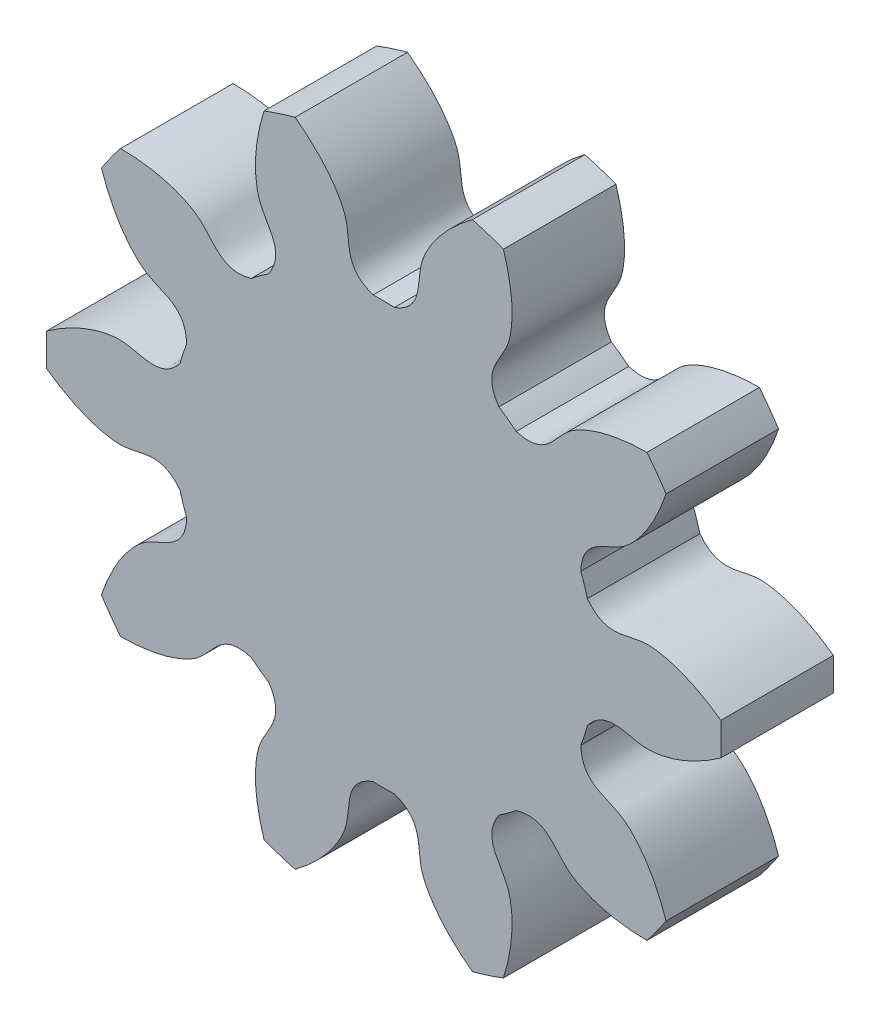
SolidWorks part; units mm, degrees
ref_plane "前视基准面" through (0, 0, 0) normal (0, 0, 1) x (1, 0, 0)
ref_plane "上视基准面" through (0, 0, 0) normal (0, 1, 0) x (1, 0, 0)
ref_plane "右视基准面" through (0, 0, 0) normal (1, 0, 0) x (0, 0, -1)
sketch "草图1" plane through (0, 0, 0) normal (0, 0, 1) x (1, 0, 0)
  circle A0 centre (0, 0) radius 12
extrude "凸台-拉伸1" add sketch "草图1" along normal blind 30
ref_axis "基准轴1" through (0, 0, -1.5) along (0, 0, 1)
sketch "草图2" plane through (0, 0, 0) normal (0, 0, 1) x (1, 0, 0)
  line L0 (0, 0) -> (0, 12) construction
  circle A0 centre (0, 0) radius 12 construction
  arc A1 (0.3809, 7.4903) -> (-0.3809, 7.4903) centre (0, 0) ccw
  arc A2 (8.5072, 13.3886) -> (-8.5072, 13.3886) centre (0, 0) ccw
  spline S0 degree 3 poles (0.3809, 7.4903) (1.4509, 7.8811) (1.1477, 8.7412) (1.3773, 9.4493) (1.389, 9.4831) (1.4027, 9.5201) (1.4184, 9.5604) (1.4364, 9.6038) (1.4568, 9.6502) (1.4797, 9.6997) (1.5052, 9.7521) (1.5335, 9.8073) (1.5646, 9.8653) (1.5987, 9.9258) (1.636, 9.989) (1.6765, 10.0545) (1.7203, 10.1225) (1.7675, 10.1926) (1.8184, 10.2648) (1.8728, 10.3391) (1.9311, 10.4152) (1.9932, 10.4931) (2.0592, 10.5726) (2.1293, 10.6537) (2.2035, 10.7361) (2.2819, 10.8197) (2.3646, 10.9045) (2.4516, 10.9902) (2.5431, 11.0768) (2.639, 11.164) (2.7395, 11.2518) (2.8447, 11.3399) (2.9545, 11.4283) (3.069, 11.5168) (3.1883, 11.6052) (3.3124, 11.6934) (3.4413, 11.7812) (3.5751, 11.8685) (3.7138, 11.9551) (3.8575, 12.0408) (4.0061, 12.1254) (4.1597, 12.2089) (4.3182, 12.291) (4.4818, 12.3716) (4.6503, 12.4505) (4.8238, 12.5275) (5.0022, 12.6025) (5.1856, 12.6753) (5.374, 12.7458) (5.5673, 12.8137) (5.7655, 12.8789) (5.9685, 12.9412) (6.1763, 13.0005) (6.389, 13.0566) (6.6063, 13.1093) (6.8284, 13.1585) (7.055, 13.2039) (7.2863, 13.2455) (7.522, 13.283) (7.7621, 13.3164) (8.0906, 13.3553) (8.3397, 13.3772) (8.5072, 13.3886) knots 0 0 0 0 0.201721 0.204697 0.208023 0.211699 0.215726 0.220102 0.224829 0.229906 0.235332 0.241109 0.247237 0.253714 0.260541 0.267719 0.275246 0.283124 0.291352 0.29993 0.308858 0.318136 0.327765 0.337743 0.348072 0.358751 0.36978 0.381158 0.392888 0.404967 0.417396 0.430176 0.443305 0.456785 0.470615 0.484795 0.499325 0.514205 0.529435 0.545016 0.560946 0.577227 0.593858 0.610839 0.62817 0.645851 0.663882 0.682264 0.700995 0.720077 0.739509 0.759291 0.779423 0.799905 0.820737 0.84192 0.863452 0.885335 0.907568 0.930151 0.953084 1 1 1 1
  spline S1 degree 3 poles (-0.3809, 7.4903) (-1.4509, 7.8811) (-1.1477, 8.7412) (-1.3773, 9.4493) (-1.389, 9.4831) (-1.4027, 9.5201) (-1.4184, 9.5604) (-1.4364, 9.6038) (-1.4568, 9.6502) (-1.4797, 9.6997) (-1.5052, 9.7521) (-1.5335, 9.8073) (-1.5646, 9.8653) (-1.5987, 9.9258) (-1.636, 9.989) (-1.6765, 10.0545) (-1.7203, 10.1225) (-1.7675, 10.1926) (-1.8184, 10.2648) (-1.8728, 10.3391) (-1.9311, 10.4152) (-1.9932, 10.4931) (-2.0592, 10.5726) (-2.1293, 10.6537) (-2.2035, 10.7361) (-2.2819, 10.8197) (-2.3646, 10.9045) (-2.4516, 10.9902) (-2.5431, 11.0768) (-2.639, 11.164) (-2.7395, 11.2518) (-2.8447, 11.3399) (-2.9545, 11.4283) (-3.069, 11.5168) (-3.1883, 11.6052) (-3.3124, 11.6934) (-3.4413, 11.7812) (-3.5751, 11.8685) (-3.7138, 11.9551) (-3.8575, 12.0408) (-4.0061, 12.1254) (-4.1597, 12.2089) (-4.3182, 12.291) (-4.4818, 12.3716) (-4.6503, 12.4505) (-4.8238, 12.5275) (-5.0022, 12.6025) (-5.1856, 12.6753) (-5.374, 12.7458) (-5.5673, 12.8137) (-5.7655, 12.8789) (-5.9685, 12.9412) (-6.1763, 13.0005) (-6.389, 13.0566) (-6.6063, 13.1093) (-6.8284, 13.1585) (-7.055, 13.2039) (-7.2863, 13.2455) (-7.522, 13.283) (-7.7621, 13.3164) (-8.0906, 13.3553) (-8.3397, 13.3772) (-8.5072, 13.3886) knots 0 0 0 0 0.201721 0.204697 0.208023 0.211699 0.215726 0.220102 0.224829 0.229906 0.235332 0.241109 0.247237 0.253714 0.260541 0.267719 0.275246 0.283124 0.291352 0.29993 0.308858 0.318136 0.327765 0.337743 0.348072 0.358751 0.36978 0.381158 0.392888 0.404967 0.417396 0.430176 0.443305 0.456785 0.470615 0.484795 0.499325 0.514205 0.529435 0.545016 0.560946 0.577227 0.593858 0.610839 0.62817 0.645851 0.663882 0.682264 0.700995 0.720077 0.739509 0.759291 0.779423 0.799905 0.820737 0.84192 0.863452 0.885335 0.907568 0.930151 0.953084 1 1 1 1
extrude "切除-拉伸1" cut sketch "草图2" along normal through all
pattern_circular "阵列(圆周)1" count 10 every 36 about axis through (0, 0, -1.5) along (0, 0, 1) of "切除-拉伸1"
sketch "草图3" plane through (0, 0, 0) normal (0, 0, 1) x (1, 0, 0)
  circle A0 centre (0, 0) radius 10 construction
  dimension "Dn" = 20
sketch "草图4" plane through (0, 0, 30) normal (0, 0, 1) x (1, 0, 0)
  arc A20 (-4.0945, 6.2837) -> (-4.7109, 5.8359) centre (0, 0) ccw
  arc A21 (-9.3561, 7.5142) -> (-10.0376, 6.5762) centre (0, 0) ccw
  arc A22 (-7.006, 2.6769) -> (-7.2414, 1.9524) centre (0, 0) ccw
  arc A23 (-11.986, 0.5797) -> (-11.986, -0.5797) centre (0, 0) ccw
  arc A24 (-7.2414, -1.9524) -> (-7.006, -2.6769) centre (0, 0) ccw
  arc A25 (-10.0376, -6.5762) -> (-9.3561, -7.5142) centre (0, 0) ccw
  arc A26 (-4.7109, -5.8359) -> (-4.0945, -6.2837) centre (0, 0) ccw
  arc A27 (-4.2552, -11.2202) -> (-3.1525, -11.5785) centre (0, 0) ccw
  arc A28 (-0.3809, -7.4903) -> (0.3809, -7.4903) centre (0, 0) ccw
  arc A29 (3.1525, -11.5785) -> (4.2552, -11.2202) centre (0, 0) ccw
  arc A30 (4.0945, -6.2837) -> (4.7109, -5.8359) centre (0, 0) ccw
  arc A31 (9.3561, -7.5142) -> (10.0376, -6.5762) centre (0, 0) ccw
  arc A32 (7.006, -2.6769) -> (7.2414, -1.9524) centre (0, 0) ccw
  arc A33 (11.986, -0.5797) -> (11.986, 0.5797) centre (0, 0) ccw
  arc A34 (7.2414, 1.9524) -> (7.006, 2.6769) centre (0, 0) ccw
  arc A35 (10.0376, 6.5762) -> (9.3561, 7.5142) centre (0, 0) ccw
  arc A36 (4.7109, 5.8359) -> (4.0945, 6.2837) centre (0, 0) ccw
  arc A37 (4.2552, 11.2202) -> (3.1525, 11.5785) centre (0, 0) ccw
  arc A38 (0.3809, 7.4903) -> (-0.3809, 7.4903) centre (0, 0) ccw
  arc A39 (-3.1525, 11.5785) -> (-4.2552, 11.2202) centre (0, 0) ccw
  arc A40 (-4.0945, 6.2837) -> (-4.7109, 5.8359) centre (0, 0) ccw
  arc A41 (-9.3561, 7.5142) -> (-10.0376, 6.5762) centre (0, 0) ccw
  arc A42 (-7.006, 2.6769) -> (-7.2414, 1.9524) centre (0, 0) ccw
  arc A43 (-11.986, 0.5797) -> (-11.986, -0.5797) centre (0, 0) ccw
  arc A44 (-7.2414, -1.9524) -> (-7.006, -2.6769) centre (0, 0) ccw
  arc A45 (-10.0376, -6.5762) -> (-9.3561, -7.5142) centre (0, 0) ccw
  arc A46 (-4.7109, -5.8359) -> (-4.0945, -6.2837) centre (0, 0) ccw
  arc A47 (-4.2552, -11.2202) -> (-3.1525, -11.5785) centre (0, 0) ccw
  arc A48 (-0.3809, -7.4903) -> (0.3809, -7.4903) centre (0, 0) ccw
  arc A49 (3.1525, -11.5785) -> (4.2552, -11.2202) centre (0, 0) ccw
  arc A50 (4.0945, -6.2837) -> (4.7109, -5.8359) centre (0, 0) ccw
  arc A51 (9.3561, -7.5142) -> (10.0376, -6.5762) centre (0, 0) ccw
  arc A52 (7.006, -2.6769) -> (7.2414, -1.9524) centre (0, 0) ccw
  arc A53 (11.986, -0.5797) -> (11.986, 0.5797) centre (0, 0) ccw
  arc A54 (7.2414, 1.9524) -> (7.006, 2.6769) centre (0, 0) ccw
  arc A55 (10.0376, 6.5762) -> (9.3561, 7.5142) centre (0, 0) ccw
  arc A56 (4.7109, 5.8359) -> (4.0945, 6.2837) centre (0, 0) ccw
  arc A57 (4.2552, 11.2202) -> (3.1525, 11.5785) centre (0, 0) ccw
  arc A58 (0.3809, 7.4903) -> (-0.3809, 7.4903) centre (0, 0) ccw
  arc A59 (-3.1525, 11.5785) -> (-4.2552, 11.2202) centre (0, 0) ccw
  spline S20 degree 3 poles (2357.9896, 3233.0149) (-45.5111, -76.1208) (0.8912, 1.3359) (-6.6791, 6.8428) (-6.7335, 6.8799) (-6.81, 6.9276) (-6.9015, 6.9798) (-7.0083, 7.0352) (-7.1308, 7.0926) (-7.2694, 7.151) (-7.4243, 7.2091) (-7.5956, 7.2657) (-7.7836, 7.3195) (-7.9881, 7.3693) (-8.2093, 7.4139) (-8.4468, 7.452) (-8.7007, 7.4824) (-8.9705, 7.5038) (-41.9663, 8.7956) (-79.134, -211.6177) (2738.2164, 2912.7683) knots -1.870678 -1.870678 -1.870678 -1.870678 0.735149 0.738125 0.745127 0.75353 0.763333 0.774537 0.787142 0.801147 0.816552 0.833358 0.851564 0.871171 0.892178 0.914586 0.938395 0.963603 0.990213 10.164096 10.164096 10.164096 10.164096 only from (-4.7109, 5.8359) to (-9.3561, 7.5142)
  spline S21 degree 3 poles (-1900.4629, -3517.2649) (168.6597, 144.2035) (-22.0225, 35.4119) (-9.8048, 5.9626) (-9.6975, 5.7306) (-9.5878, 5.5164) (-9.4771, 5.3199) (-9.3665, 5.1408) (-9.2572, 4.9787) (-9.1505, 4.8332) (-9.0474, 4.7038) (-8.9491, 4.5901) (-8.8565, 4.4913) (-8.7709, 4.4068) (-8.693, 4.336) (-8.6239, 4.2779) (-8.5719, 4.2376) (-0.9951, -1.2604) (58.3315, 66.8063) (-2346.1255, -3241.6441) knots -8.822355 -8.822355 -8.822355 -8.822355 0.036397 0.061605 0.085414 0.107822 0.128829 0.148436 0.166642 0.183448 0.198853 0.212858 0.225463 0.236667 0.24647 0.254873 0.261875 0.264851 2.87068 2.87068 2.87068 2.87068 only from (-10.0376, 6.5762) to (-7.006, 2.6769)
  spline S22 degree 3 poles (7.3352, 4001.5555) (7.9234, -88.3337) (-0.0642, 1.6046) (-9.4256, 1.6101) (-9.4914, 1.6081) (-9.5814, 1.6018) (-9.686, 1.5902) (-9.805, 1.5722) (-9.9379, 1.5467) (-10.0843, 1.5125) (-10.2438, 1.4684) (-10.4157, 1.4134) (-10.5993, 1.3465) (-10.7941, 1.2666) (-10.9992, 1.1727) (-11.2138, 1.0639) (-11.437, 0.9392) (-11.6679, 0.7979) (-39.1213, -17.5514) (60.365, -217.7161) (503.1813, 3965.9623) knots -1.870678 -1.870678 -1.870678 -1.870678 0.735149 0.738125 0.745127 0.75353 0.763333 0.774537 0.787142 0.801147 0.816552 0.833358 0.851564 0.871171 0.892178 0.914586 0.938395 0.963603 0.990213 10.164096 10.164096 10.164096 10.164096 only from (-7.2414, 1.9524) to (-11.986, 0.5797)
  spline S23 degree 3 poles (529.8897, -3962.5911) (51.6878, 215.7988) (-38.6312, 15.7043) (-11.437, -0.9392) (-11.2138, -1.0639) (-10.9992, -1.1727) (-10.7941, -1.2666) (-10.5993, -1.3465) (-10.4157, -1.4134) (-10.2438, -1.4684) (-10.0843, -1.5125) (-9.9379, -1.5467) (-9.805, -1.5722) (-9.686, -1.5902) (-9.5814, -1.6018) (-9.4914, -1.6081) (-9.4256, -1.6101) (-0.0642, -1.6046) (7.9234, 88.3338) (7.3352, -4001.5632) knots -8.822355 -8.822355 -8.822355 -8.822355 0.036397 0.061605 0.085414 0.107822 0.128829 0.148436 0.166642 0.183448 0.198853 0.212858 0.225463 0.236667 0.24647 0.254873 0.261875 0.264851 2.87068 2.87068 2.87068 2.87068 only from (-11.986, -0.5797) to (-7.2414, -1.9524)
  spline S24 degree 3 poles (-2346.121, 3241.6379) (58.3315, -66.8062) (-0.9952, 1.2604) (-8.5719, -4.2376) (-8.6239, -4.2779) (-8.693, -4.336) (-8.7709, -4.4068) (-8.8565, -4.4913) (-8.9491, -4.5901) (-9.0474, -4.7038) (-9.1505, -4.8332) (-9.2572, -4.9787) (-9.3665, -5.1408) (-9.4771, -5.3199) (-9.5878, -5.5164) (-9.6975, -5.7306) (-9.8048, -5.9626) (-9.9085, -6.2127) (-21.3334, -37.1943) (176.8067, -140.6544) (-1924.0519, 3504.2934) knots -1.870678 -1.870678 -1.870678 -1.870678 0.735149 0.738125 0.745127 0.75353 0.763333 0.774537 0.787142 0.801147 0.816552 0.833358 0.851564 0.871171 0.892178 0.914586 0.938395 0.963603 0.990213 10.164096 10.164096 10.164096 10.164096 only from (-7.006, -2.6769) to (-10.0376, -6.5762)
  spline S25 degree 3 poles (2757.8424, -2894.3422) (-85.027, 204.9662) (-40.4841, -10.0018) (-8.7007, -7.4824) (-8.4468, -7.452) (-8.2093, -7.4139) (-7.9881, -7.3693) (-7.7836, -7.3195) (-7.5956, -7.2657) (-7.4243, -7.2091) (-7.2694, -7.151) (-7.1308, -7.0926) (-7.0083, -7.0352) (-6.9015, -6.9798) (-6.81, -6.9277) (-6.7335, -6.8799) (-6.6791, -6.8428) (0.8912, -1.3359) (-45.5111, 76.1209) (2357.9941, -3233.0211) knots -8.822355 -8.822355 -8.822355 -8.822355 0.036397 0.061605 0.085414 0.107822 0.128829 0.148436 0.166642 0.183448 0.198853 0.212858 0.225463 0.236667 0.24647 0.254873 0.261875 0.264851 2.87068 2.87068 2.87068 2.87068 only from (-9.3561, -7.5142) to (-4.7109, -5.8359)
  spline S26 degree 3 poles (-3803.4388, 1243.5248) (86.4588, -19.761) (-1.546, 0.4348) (-4.444, -8.4668) (-4.4624, -8.5299) (-4.4842, -8.6175) (-4.5055, -8.7206) (-4.5252, -8.8393) (-4.542, -8.9735) (-4.5547, -9.1234) (-4.562, -9.2886) (-4.5629, -9.4691) (-4.556, -9.6645) (-4.5402, -9.8744) (-4.5142, -10.0985) (-4.4771, -10.3362) (-4.4275, -10.587) (-4.3645, -10.8503) (4.6032, -42.6303) (225.7141, -9.8674) (-3616.3627, 1704.1036) knots -1.870678 -1.870678 -1.870678 -1.870678 0.735149 0.738125 0.745127 0.75353 0.763333 0.774537 0.787142 0.801147 0.816552 0.833358 0.851564 0.871171 0.892178 0.914586 0.938395 0.963603 0.990213 10.164096 10.164096 10.164096 10.164096 only from (-4.0945, -6.2837) to (-4.2552, -11.2202)
  spline S27 degree 3 poles (3932.393, -720.553) (-189.2644, 115.8435) (-26.8734, -31.8875) (-2.641, -11.1675) (-2.4534, -10.9937) (-2.2836, -10.8233) (-2.131, -10.6572) (-1.9948, -10.4967) (-1.8744, -10.3427) (-1.769, -10.1962) (-1.6778, -10.0581) (-1.6, -9.9295) (-1.5346, -9.8109) (-1.4808, -9.7034) (-1.4375, -9.6074) (-1.4036, -9.5238) (-1.3814, -9.4619) (1.5063, -0.5569) (-81.562, 34.8323) (3807.9794, -1229.5749) knots -8.822355 -8.822355 -8.822355 -8.822355 0.036397 0.061605 0.085414 0.107822 0.128829 0.148436 0.166642 0.183448 0.198853 0.212858 0.225463 0.236667 0.24647 0.254873 0.261875 0.264851 2.87068 2.87068 2.87068 2.87068 only from (-3.1525, -11.5785) to (-0.3809, -7.4903)
  spline S28 degree 3 poles (-3807.9721, -1229.5725) (81.5619, 34.8323) (-1.5063, -0.557) (1.3814, -9.4619) (1.4036, -9.5238) (1.4375, -9.6074) (1.4808, -9.7034) (1.5346, -9.8109) (1.6, -9.9295) (1.6778, -10.0581) (1.769, -10.1962) (1.8744, -10.3427) (1.9948, -10.4967) (2.131, -10.6572) (2.2836, -10.8233) (2.4534, -10.9937) (2.641, -11.1675) (2.8467, -11.3434) (28.7815, -31.7829) (188.4065, 124.6885) (-3927.3458, -746.9958) knots -1.870678 -1.870678 -1.870678 -1.870678 0.735149 0.738125 0.745127 0.75353 0.763333 0.774537 0.787142 0.801147 0.816552 0.833358 0.851564 0.871171 0.892178 0.914586 0.938395 0.963603 0.990213 10.164096 10.164096 10.164096 10.164096 only from (0.3809, -7.4903) to (3.1525, -11.5785)
  spline S29 degree 3 poles (3604.9032, 1728.463) (-221.2093, -17.5274) (-2.998, -41.5933) (4.4275, -10.587) (4.4771, -10.3362) (4.5142, -10.0985) (4.5402, -9.8744) (4.556, -9.6645) (4.5629, -9.4691) (4.562, -9.2886) (4.5547, -9.1234) (4.542, -8.9735) (4.5252, -8.8393) (4.5055, -8.7206) (4.4842, -8.6175) (4.4624, -8.5299) (4.444, -8.4668) (1.5459, 0.4348) (-86.459, -19.761) (3803.446, 1243.5272) knots -8.822355 -8.822355 -8.822355 -8.822355 0.036397 0.061605 0.085414 0.107822 0.128829 0.148436 0.166642 0.183448 0.198853 0.212858 0.225463 0.236667 0.24647 0.254873 0.261875 0.264851 2.87068 2.87068 2.87068 2.87068 only from (4.2552, -11.2202) to (4.0945, -6.2837)
  spline S30 degree 3 poles (-2357.9896, -3233.0149) (45.5111, 76.1208) (-0.8912, -1.3359) (6.6791, -6.8428) (6.7335, -6.8799) (6.81, -6.9276) (6.9015, -6.9798) (7.0083, -7.0352) (7.1308, -7.0926) (7.2694, -7.151) (7.4243, -7.2091) (7.5956, -7.2657) (7.7836, -7.3195) (7.9881, -7.3693) (8.2093, -7.4139) (8.4468, -7.452) (8.7007, -7.4824) (8.9705, -7.5038) (41.9663, -8.7956) (79.134, 211.6177) (-2738.2164, -2912.7683) knots -1.870678 -1.870678 -1.870678 -1.870678 0.735149 0.738125 0.745127 0.75353 0.763333 0.774537 0.787142 0.801147 0.816552 0.833358 0.851564 0.871171 0.892178 0.914586 0.938395 0.963603 0.990213 10.164096 10.164096 10.164096 10.164096 only from (4.7109, -5.8359) to (9.3561, -7.5142)
  spline S31 degree 3 poles (1900.4629, 3517.2649) (-168.6597, -144.2035) (22.0225, -35.4119) (9.8048, -5.9626) (9.6975, -5.7306) (9.5878, -5.5164) (9.4771, -5.3199) (9.3665, -5.1408) (9.2572, -4.9787) (9.1505, -4.8332) (9.0474, -4.7038) (8.9491, -4.5901) (8.8565, -4.4913) (8.7709, -4.4068) (8.693, -4.336) (8.6239, -4.2779) (8.5719, -4.2376) (0.9951, 1.2604) (-58.3315, -66.8063) (2346.1255, 3241.6441) knots -8.822355 -8.822355 -8.822355 -8.822355 0.036397 0.061605 0.085414 0.107822 0.128829 0.148436 0.166642 0.183448 0.198853 0.212858 0.225463 0.236667 0.24647 0.254873 0.261875 0.264851 2.87068 2.87068 2.87068 2.87068 only from (10.0376, -6.5762) to (7.006, -2.6769)
  spline S32 degree 3 poles (-7.3352, -4001.5555) (-7.9234, 88.3337) (0.0642, -1.6046) (9.4256, -1.6101) (9.4914, -1.6081) (9.5814, -1.6018) (9.686, -1.5902) (9.805, -1.5722) (9.9379, -1.5467) (10.0843, -1.5125) (10.2438, -1.4684) (10.4157, -1.4134) (10.5993, -1.3465) (10.7941, -1.2666) (10.9992, -1.1727) (11.2138, -1.0639) (11.437, -0.9392) (11.6679, -0.7979) (39.1213, 17.5514) (-60.365, 217.7161) (-503.1813, -3965.9623) knots -1.870678 -1.870678 -1.870678 -1.870678 0.735149 0.738125 0.745127 0.75353 0.763333 0.774537 0.787142 0.801147 0.816552 0.833358 0.851564 0.871171 0.892178 0.914586 0.938395 0.963603 0.990213 10.164096 10.164096 10.164096 10.164096 only from (7.2414, -1.9524) to (11.986, -0.5797)
  spline S33 degree 3 poles (-529.8897, 3962.5911) (-51.6878, -215.7988) (38.6312, -15.7043) (11.437, 0.9392) (11.2138, 1.0639) (10.9992, 1.1727) (10.7941, 1.2666) (10.5993, 1.3465) (10.4157, 1.4134) (10.2438, 1.4684) (10.0843, 1.5125) (9.9379, 1.5467) (9.805, 1.5722) (9.686, 1.5902) (9.5814, 1.6018) (9.4914, 1.6081) (9.4256, 1.6101) (0.0642, 1.6046) (-7.9234, -88.3338) (-7.3352, 4001.5632) knots -8.822355 -8.822355 -8.822355 -8.822355 0.036397 0.061605 0.085414 0.107822 0.128829 0.148436 0.166642 0.183448 0.198853 0.212858 0.225463 0.236667 0.24647 0.254873 0.261875 0.264851 2.87068 2.87068 2.87068 2.87068 only from (11.986, 0.5797) to (7.2414, 1.9524)
  spline S34 degree 3 poles (2346.121, -3241.6379) (-58.3315, 66.8062) (0.9952, -1.2604) (8.5719, 4.2376) (8.6239, 4.2779) (8.693, 4.336) (8.7709, 4.4068) (8.8565, 4.4913) (8.9491, 4.5901) (9.0474, 4.7038) (9.1505, 4.8332) (9.2572, 4.9787) (9.3665, 5.1408) (9.4771, 5.3199) (9.5878, 5.5164) (9.6975, 5.7306) (9.8048, 5.9626) (9.9085, 6.2127) (21.3334, 37.1943) (-176.8067, 140.6544) (1924.0519, -3504.2934) knots -1.870678 -1.870678 -1.870678 -1.870678 0.735149 0.738125 0.745127 0.75353 0.763333 0.774537 0.787142 0.801147 0.816552 0.833358 0.851564 0.871171 0.892178 0.914586 0.938395 0.963603 0.990213 10.164096 10.164096 10.164096 10.164096 only from (7.006, 2.6769) to (10.0376, 6.5762)
  spline S35 degree 3 poles (-2757.8424, 2894.3422) (85.027, -204.9662) (40.4841, 10.0018) (8.7007, 7.4824) (8.4468, 7.452) (8.2093, 7.4139) (7.9881, 7.3693) (7.7836, 7.3195) (7.5956, 7.2657) (7.4243, 7.2091) (7.2694, 7.151) (7.1308, 7.0926) (7.0083, 7.0352) (6.9015, 6.9798) (6.81, 6.9277) (6.7335, 6.8799) (6.6791, 6.8428) (-0.8912, 1.3359) (45.5111, -76.1209) (-2357.9941, 3233.0211) knots -8.822355 -8.822355 -8.822355 -8.822355 0.036397 0.061605 0.085414 0.107822 0.128829 0.148436 0.166642 0.183448 0.198853 0.212858 0.225463 0.236667 0.24647 0.254873 0.261875 0.264851 2.87068 2.87068 2.87068 2.87068 only from (9.3561, 7.5142) to (4.7109, 5.8359)
  spline S36 degree 3 poles (3803.4388, -1243.5248) (-86.4588, 19.761) (1.546, -0.4348) (4.444, 8.4668) (4.4624, 8.5299) (4.4842, 8.6175) (4.5055, 8.7206) (4.5252, 8.8393) (4.542, 8.9735) (4.5547, 9.1234) (4.562, 9.2886) (4.5629, 9.4691) (4.556, 9.6645) (4.5402, 9.8744) (4.5142, 10.0985) (4.4771, 10.3362) (4.4275, 10.587) (4.3645, 10.8503) (-4.6032, 42.6303) (-225.7141, 9.8674) (3616.3627, -1704.1036) knots -1.870678 -1.870678 -1.870678 -1.870678 0.735149 0.738125 0.745127 0.75353 0.763333 0.774537 0.787142 0.801147 0.816552 0.833358 0.851564 0.871171 0.892178 0.914586 0.938395 0.963603 0.990213 10.164096 10.164096 10.164096 10.164096 only from (4.0945, 6.2837) to (4.2552, 11.2202)
  spline S37 degree 3 poles (-3932.393, 720.553) (189.2644, -115.8435) (26.8734, 31.8875) (2.641, 11.1675) (2.4534, 10.9937) (2.2836, 10.8233) (2.131, 10.6572) (1.9948, 10.4967) (1.8744, 10.3427) (1.769, 10.1962) (1.6778, 10.0581) (1.6, 9.9295) (1.5346, 9.8109) (1.4808, 9.7034) (1.4375, 9.6074) (1.4036, 9.5238) (1.3814, 9.4619) (-1.5063, 0.5569) (81.562, -34.8323) (-3807.9794, 1229.5749) knots -8.822355 -8.822355 -8.822355 -8.822355 0.036397 0.061605 0.085414 0.107822 0.128829 0.148436 0.166642 0.183448 0.198853 0.212858 0.225463 0.236667 0.24647 0.254873 0.261875 0.264851 2.87068 2.87068 2.87068 2.87068 only from (3.1525, 11.5785) to (0.3809, 7.4903)
  spline S38 degree 3 poles (3807.9721, 1229.5725) (-81.5619, -34.8323) (1.5063, 0.557) (-1.3814, 9.4619) (-1.4036, 9.5238) (-1.4375, 9.6074) (-1.4808, 9.7034) (-1.5346, 9.8109) (-1.6, 9.9295) (-1.6778, 10.0581) (-1.769, 10.1962) (-1.8744, 10.3427) (-1.9948, 10.4967) (-2.131, 10.6572) (-2.2836, 10.8233) (-2.4534, 10.9937) (-2.641, 11.1675) (-2.8467, 11.3434) (-28.7815, 31.7829) (-188.4065, -124.6885) (3927.3458, 746.9958) knots -1.870678 -1.870678 -1.870678 -1.870678 0.735149 0.738125 0.745127 0.75353 0.763333 0.774537 0.787142 0.801147 0.816552 0.833358 0.851564 0.871171 0.892178 0.914586 0.938395 0.963603 0.990213 10.164096 10.164096 10.164096 10.164096 only from (-0.3809, 7.4903) to (-3.1525, 11.5785)
  spline S39 degree 3 poles (-3604.9032, -1728.463) (221.2093, 17.5274) (2.998, 41.5933) (-4.4275, 10.587) (-4.4771, 10.3362) (-4.5142, 10.0985) (-4.5402, 9.8744) (-4.556, 9.6645) (-4.5629, 9.4691) (-4.562, 9.2886) (-4.5547, 9.1234) (-4.542, 8.9735) (-4.5252, 8.8393) (-4.5055, 8.7206) (-4.4842, 8.6175) (-4.4624, 8.5299) (-4.444, 8.4668) (-1.5459, -0.4348) (86.459, 19.761) (-3803.446, -1243.5272) knots -8.822355 -8.822355 -8.822355 -8.822355 0.036397 0.061605 0.085414 0.107822 0.128829 0.148436 0.166642 0.183448 0.198853 0.212858 0.225463 0.236667 0.24647 0.254873 0.261875 0.264851 2.87068 2.87068 2.87068 2.87068 only from (-4.2552, 11.2202) to (-4.0945, 6.2837)
  spline S40 degree 3 poles (-4.7109, 5.8359) (-5.8062, 5.5232) (-6.0664, 6.3972) (-6.6791, 6.8428) (-6.7335, 6.8799) (-6.81, 6.9276) (-6.9015, 6.9798) (-7.0083, 7.0352) (-7.1308, 7.0926) (-7.2694, 7.151) (-7.4243, 7.2091) (-7.5956, 7.2657) (-7.7836, 7.3195) (-7.9881, 7.3693) (-8.2093, 7.4139) (-8.4468, 7.452) (-8.7007, 7.4824) (-8.9705, 7.5038) (-9.1908, 7.5124) (-9.3211, 7.514) (-9.3561, 7.5142) knots 0.533428 0.533428 0.533428 0.533428 0.735149 0.738125 0.745127 0.75353 0.763333 0.774537 0.787142 0.801147 0.816552 0.833358 0.851564 0.871171 0.892178 0.914586 0.938395 0.963603 0.990213 1 1 1 1
  spline S41 degree 3 poles (-10.0376, 6.5762) (-9.9967, 6.4525) (-9.922, 6.245) (-9.8048, 5.9626) (-9.6975, 5.7306) (-9.5878, 5.5164) (-9.4771, 5.3199) (-9.3665, 5.1408) (-9.2572, 4.9787) (-9.1505, 4.8332) (-9.0474, 4.7038) (-8.9491, 4.5901) (-8.8565, 4.4913) (-8.7709, 4.4068) (-8.693, 4.336) (-8.6239, 4.2779) (-8.5719, 4.2376) (-7.9587, 3.7927) (-7.0471, 3.8153) (-7.006, 2.6769) knots 0 0 0 0 0.036397 0.061605 0.085414 0.107822 0.128829 0.148436 0.166642 0.183448 0.198853 0.212858 0.225463 0.236667 0.24647 0.254873 0.261875 0.264851 0.466572 0.466572 0.466572 0.466572
  spline S42 degree 3 poles (-7.2414, 1.9524) (-7.9437, 1.0556) (-8.668, 1.6097) (-9.4256, 1.6101) (-9.4914, 1.6081) (-9.5814, 1.6018) (-9.686, 1.5902) (-9.805, 1.5722) (-9.9379, 1.5467) (-10.0843, 1.5125) (-10.2438, 1.4684) (-10.4157, 1.4134) (-10.5993, 1.3465) (-10.7941, 1.2666) (-10.9992, 1.1727) (-11.2138, 1.0639) (-11.437, 0.9392) (-11.6679, 0.7979) (-11.8512, 0.6754) (-11.9575, 0.6002) (-11.986, 0.5797) knots 0.533428 0.533428 0.533428 0.533428 0.735149 0.738125 0.745127 0.75353 0.763333 0.774537 0.787142 0.801147 0.816552 0.833358 0.851564 0.871171 0.892178 0.914586 0.938395 0.963603 0.990213 1 1 1 1
  spline S43 degree 3 poles (-11.986, -0.5797) (-11.8802, -0.6557) (-11.6978, -0.7797) (-11.437, -0.9392) (-11.2138, -1.0639) (-10.9992, -1.1727) (-10.7941, -1.2666) (-10.5993, -1.3465) (-10.4157, -1.4134) (-10.2438, -1.4684) (-10.0843, -1.5125) (-9.9379, -1.5467) (-9.805, -1.5722) (-9.686, -1.5902) (-9.5814, -1.6018) (-9.4914, -1.6081) (-9.4256, -1.6101) (-8.668, -1.6097) (-7.9437, -1.0556) (-7.2414, -1.9524) knots 0 0 0 0 0.036397 0.061605 0.085414 0.107822 0.128829 0.148436 0.166642 0.183448 0.198853 0.212858 0.225463 0.236667 0.24647 0.254873 0.261875 0.264851 0.466572 0.466572 0.466572 0.466572
  spline S44 degree 3 poles (-7.006, -2.6769) (-7.0471, -3.8153) (-7.9587, -3.7927) (-8.5719, -4.2376) (-8.6239, -4.2779) (-8.693, -4.336) (-8.7709, -4.4068) (-8.8565, -4.4913) (-8.9491, -4.5901) (-9.0474, -4.7038) (-9.1505, -4.8332) (-9.2572, -4.9787) (-9.3665, -5.1408) (-9.4771, -5.3199) (-9.5878, -5.5164) (-9.6975, -5.7306) (-9.8048, -5.9626) (-9.9085, -6.2127) (-9.9848, -6.4196) (-10.0266, -6.5429) (-10.0376, -6.5762) knots 0.533428 0.533428 0.533428 0.533428 0.735149 0.738125 0.745127 0.75353 0.763333 0.774537 0.787142 0.801147 0.816552 0.833358 0.851564 0.871171 0.892178 0.914586 0.938395 0.963603 0.990213 1 1 1 1
  spline S45 degree 3 poles (-9.3561, -7.5142) (-9.2259, -7.5135) (-9.0054, -7.5065) (-8.7007, -7.4824) (-8.4468, -7.452) (-8.2093, -7.4139) (-7.9881, -7.3693) (-7.7836, -7.3195) (-7.5956, -7.2657) (-7.4243, -7.2091) (-7.2694, -7.151) (-7.1308, -7.0926) (-7.0083, -7.0352) (-6.9015, -6.9798) (-6.81, -6.9277) (-6.7335, -6.8799) (-6.6791, -6.8428) (-6.0664, -6.3972) (-5.8062, -5.5232) (-4.7109, -5.8359) knots 0 0 0 0 0.036397 0.061605 0.085414 0.107822 0.128829 0.148436 0.166642 0.183448 0.198853 0.212858 0.225463 0.236667 0.24647 0.254873 0.261875 0.264851 0.466572 0.466572 0.466572 0.466572
  spline S46 degree 3 poles (-4.0945, -6.2837) (-3.4586, -7.2288) (-4.2094, -7.7464) (-4.444, -8.4668) (-4.4624, -8.5299) (-4.4842, -8.6175) (-4.5055, -8.7206) (-4.5252, -8.8393) (-4.542, -8.9735) (-4.5547, -9.1234) (-4.562, -9.2886) (-4.5629, -9.4691) (-4.556, -9.6645) (-4.5402, -9.8744) (-4.5142, -10.0985) (-4.4771, -10.3362) (-4.4275, -10.587) (-4.3645, -10.8503) (-4.3046, -11.0625) (-4.2659, -11.1868) (-4.2552, -11.2202) knots 0.533428 0.533428 0.533428 0.533428 0.735149 0.738125 0.745127 0.75353 0.763333 0.774537 0.787142 0.801147 0.816552 0.833358 0.851564 0.871171 0.892178 0.914586 0.938395 0.963603 0.990213 1 1 1 1
  spline S47 degree 3 poles (-3.1525, -11.5785) (-3.0476, -11.5014) (-2.8733, -11.3662) (-2.641, -11.1675) (-2.4534, -10.9937) (-2.2836, -10.8233) (-2.131, -10.6572) (-1.9948, -10.4967) (-1.8744, -10.3427) (-1.769, -10.1962) (-1.6778, -10.0581) (-1.6, -9.9295) (-1.5346, -9.8109) (-1.4808, -9.7034) (-1.4375, -9.6074) (-1.4036, -9.5238) (-1.3814, -9.4619) (-1.1477, -8.7412) (-1.4509, -7.8811) (-0.3809, -7.4903) knots 0 0 0 0 0.036397 0.061605 0.085414 0.107822 0.128829 0.148436 0.166642 0.183448 0.198853 0.212858 0.225463 0.236667 0.24647 0.254873 0.261875 0.264851 0.466572 0.466572 0.466572 0.466572
  spline S48 degree 3 poles (0.3809, -7.4903) (1.4509, -7.8811) (1.1477, -8.7412) (1.3814, -9.4619) (1.4036, -9.5238) (1.4375, -9.6074) (1.4808, -9.7034) (1.5346, -9.8109) (1.6, -9.9295) (1.6778, -10.0581) (1.769, -10.1962) (1.8744, -10.3427) (1.9948, -10.4967) (2.131, -10.6572) (2.2836, -10.8233) (2.4534, -10.9937) (2.641, -11.1675) (2.8467, -11.3434) (3.0199, -11.4799) (3.1243, -11.5578) (3.1525, -11.5785) knots 0.533428 0.533428 0.533428 0.533428 0.735149 0.738125 0.745127 0.75353 0.763333 0.774537 0.787142 0.801147 0.816552 0.833358 0.851564 0.871171 0.892178 0.914586 0.938395 0.963603 0.990213 1 1 1 1
  spline S49 degree 3 poles (4.2552, -11.2202) (4.2948, -11.0961) (4.3563, -10.8843) (4.4275, -10.587) (4.4771, -10.3362) (4.5142, -10.0985) (4.5402, -9.8744) (4.556, -9.6645) (4.5629, -9.4691) (4.562, -9.2886) (4.5547, -9.1234) (4.542, -8.9735) (4.5252, -8.8393) (4.5055, -8.7206) (4.4842, -8.6175) (4.4624, -8.5299) (4.444, -8.4668) (4.2094, -7.7464) (3.4586, -7.2288) (4.0945, -6.2837) knots 0 0 0 0 0.036397 0.061605 0.085414 0.107822 0.128829 0.148436 0.166642 0.183448 0.198853 0.212858 0.225463 0.236667 0.24647 0.254873 0.261875 0.264851 0.466572 0.466572 0.466572 0.466572
  spline S50 degree 3 poles (4.7109, -5.8359) (5.8062, -5.5232) (6.0664, -6.3972) (6.6791, -6.8428) (6.7335, -6.8799) (6.81, -6.9276) (6.9015, -6.9798) (7.0083, -7.0352) (7.1308, -7.0926) (7.2694, -7.151) (7.4243, -7.2091) (7.5956, -7.2657) (7.7836, -7.3195) (7.9881, -7.3693) (8.2093, -7.4139) (8.4468, -7.452) (8.7007, -7.4824) (8.9705, -7.5038) (9.1908, -7.5124) (9.3211, -7.514) (9.3561, -7.5142) knots 0.533428 0.533428 0.533428 0.533428 0.735149 0.738125 0.745127 0.75353 0.763333 0.774537 0.787142 0.801147 0.816552 0.833358 0.851564 0.871171 0.892178 0.914586 0.938395 0.963603 0.990213 1 1 1 1
  spline S51 degree 3 poles (10.0376, -6.5762) (9.9967, -6.4525) (9.922, -6.245) (9.8048, -5.9626) (9.6975, -5.7306) (9.5878, -5.5164) (9.4771, -5.3199) (9.3665, -5.1408) (9.2572, -4.9787) (9.1505, -4.8332) (9.0474, -4.7038) (8.9491, -4.5901) (8.8565, -4.4913) (8.7709, -4.4068) (8.693, -4.336) (8.6239, -4.2779) (8.5719, -4.2376) (7.9587, -3.7927) (7.0471, -3.8153) (7.006, -2.6769) knots 0 0 0 0 0.036397 0.061605 0.085414 0.107822 0.128829 0.148436 0.166642 0.183448 0.198853 0.212858 0.225463 0.236667 0.24647 0.254873 0.261875 0.264851 0.466572 0.466572 0.466572 0.466572
  spline S52 degree 3 poles (7.2414, -1.9524) (7.9437, -1.0556) (8.668, -1.6097) (9.4256, -1.6101) (9.4914, -1.6081) (9.5814, -1.6018) (9.686, -1.5902) (9.805, -1.5722) (9.9379, -1.5467) (10.0843, -1.5125) (10.2438, -1.4684) (10.4157, -1.4134) (10.5993, -1.3465) (10.7941, -1.2666) (10.9992, -1.1727) (11.2138, -1.0639) (11.437, -0.9392) (11.6679, -0.7979) (11.8512, -0.6754) (11.9575, -0.6002) (11.986, -0.5797) knots 0.533428 0.533428 0.533428 0.533428 0.735149 0.738125 0.745127 0.75353 0.763333 0.774537 0.787142 0.801147 0.816552 0.833358 0.851564 0.871171 0.892178 0.914586 0.938395 0.963603 0.990213 1 1 1 1
  spline S53 degree 3 poles (11.986, 0.5797) (11.8802, 0.6557) (11.6978, 0.7797) (11.437, 0.9392) (11.2138, 1.0639) (10.9992, 1.1727) (10.7941, 1.2666) (10.5993, 1.3465) (10.4157, 1.4134) (10.2438, 1.4684) (10.0843, 1.5125) (9.9379, 1.5467) (9.805, 1.5722) (9.686, 1.5902) (9.5814, 1.6018) (9.4914, 1.6081) (9.4256, 1.6101) (8.668, 1.6097) (7.9437, 1.0556) (7.2414, 1.9524) knots 0 0 0 0 0.036397 0.061605 0.085414 0.107822 0.128829 0.148436 0.166642 0.183448 0.198853 0.212858 0.225463 0.236667 0.24647 0.254873 0.261875 0.264851 0.466572 0.466572 0.466572 0.466572
  spline S54 degree 3 poles (7.006, 2.6769) (7.0471, 3.8153) (7.9587, 3.7927) (8.5719, 4.2376) (8.6239, 4.2779) (8.693, 4.336) (8.7709, 4.4068) (8.8565, 4.4913) (8.9491, 4.5901) (9.0474, 4.7038) (9.1505, 4.8332) (9.2572, 4.9787) (9.3665, 5.1408) (9.4771, 5.3199) (9.5878, 5.5164) (9.6975, 5.7306) (9.8048, 5.9626) (9.9085, 6.2127) (9.9848, 6.4196) (10.0266, 6.5429) (10.0376, 6.5762) knots 0.533428 0.533428 0.533428 0.533428 0.735149 0.738125 0.745127 0.75353 0.763333 0.774537 0.787142 0.801147 0.816552 0.833358 0.851564 0.871171 0.892178 0.914586 0.938395 0.963603 0.990213 1 1 1 1
  spline S55 degree 3 poles (9.3561, 7.5142) (9.2259, 7.5135) (9.0054, 7.5065) (8.7007, 7.4824) (8.4468, 7.452) (8.2093, 7.4139) (7.9881, 7.3693) (7.7836, 7.3195) (7.5956, 7.2657) (7.4243, 7.2091) (7.2694, 7.151) (7.1308, 7.0926) (7.0083, 7.0352) (6.9015, 6.9798) (6.81, 6.9277) (6.7335, 6.8799) (6.6791, 6.8428) (6.0664, 6.3972) (5.8062, 5.5232) (4.7109, 5.8359) knots 0 0 0 0 0.036397 0.061605 0.085414 0.107822 0.128829 0.148436 0.166642 0.183448 0.198853 0.212858 0.225463 0.236667 0.24647 0.254873 0.261875 0.264851 0.466572 0.466572 0.466572 0.466572
  spline S56 degree 3 poles (4.0945, 6.2837) (3.4586, 7.2288) (4.2094, 7.7464) (4.444, 8.4668) (4.4624, 8.5299) (4.4842, 8.6175) (4.5055, 8.7206) (4.5252, 8.8393) (4.542, 8.9735) (4.5547, 9.1234) (4.562, 9.2886) (4.5629, 9.4691) (4.556, 9.6645) (4.5402, 9.8744) (4.5142, 10.0985) (4.4771, 10.3362) (4.4275, 10.587) (4.3645, 10.8503) (4.3046, 11.0625) (4.2659, 11.1868) (4.2552, 11.2202) knots 0.533428 0.533428 0.533428 0.533428 0.735149 0.738125 0.745127 0.75353 0.763333 0.774537 0.787142 0.801147 0.816552 0.833358 0.851564 0.871171 0.892178 0.914586 0.938395 0.963603 0.990213 1 1 1 1
  spline S57 degree 3 poles (3.1525, 11.5785) (3.0476, 11.5014) (2.8733, 11.3662) (2.641, 11.1675) (2.4534, 10.9937) (2.2836, 10.8233) (2.131, 10.6572) (1.9948, 10.4967) (1.8744, 10.3427) (1.769, 10.1962) (1.6778, 10.0581) (1.6, 9.9295) (1.5346, 9.8109) (1.4808, 9.7034) (1.4375, 9.6074) (1.4036, 9.5238) (1.3814, 9.4619) (1.1477, 8.7412) (1.4509, 7.8811) (0.3809, 7.4903) knots 0 0 0 0 0.036397 0.061605 0.085414 0.107822 0.128829 0.148436 0.166642 0.183448 0.198853 0.212858 0.225463 0.236667 0.24647 0.254873 0.261875 0.264851 0.466572 0.466572 0.466572 0.466572
  spline S58 degree 3 poles (-0.3809, 7.4903) (-1.4509, 7.8811) (-1.1477, 8.7412) (-1.3814, 9.4619) (-1.4036, 9.5238) (-1.4375, 9.6074) (-1.4808, 9.7034) (-1.5346, 9.8109) (-1.6, 9.9295) (-1.6778, 10.0581) (-1.769, 10.1962) (-1.8744, 10.3427) (-1.9948, 10.4967) (-2.131, 10.6572) (-2.2836, 10.8233) (-2.4534, 10.9937) (-2.641, 11.1675) (-2.8467, 11.3434) (-3.0199, 11.4799) (-3.1243, 11.5578) (-3.1525, 11.5785) knots 0.533428 0.533428 0.533428 0.533428 0.735149 0.738125 0.745127 0.75353 0.763333 0.774537 0.787142 0.801147 0.816552 0.833358 0.851564 0.871171 0.892178 0.914586 0.938395 0.963603 0.990213 1 1 1 1
  spline S59 degree 3 poles (-4.2552, 11.2202) (-4.2948, 11.0961) (-4.3563, 10.8843) (-4.4275, 10.587) (-4.4771, 10.3362) (-4.5142, 10.0985) (-4.5402, 9.8744) (-4.556, 9.6645) (-4.5629, 9.4691) (-4.562, 9.2886) (-4.5547, 9.1234) (-4.542, 8.9735) (-4.5252, 8.8393) (-4.5055, 8.7206) (-4.4842, 8.6175) (-4.4624, 8.5299) (-4.444, 8.4668) (-4.2094, 7.7464) (-3.4586, 7.2288) (-4.0945, 6.2837) knots 0 0 0 0 0.036397 0.061605 0.085414 0.107822 0.128829 0.148436 0.166642 0.183448 0.198853 0.212858 0.225463 0.236667 0.24647 0.254873 0.261875 0.264851 0.466572 0.466572 0.466572 0.466572
  dimension "D1" = 0
extrude "切除-拉伸2" cut sketch "草图4" against normal blind 26
